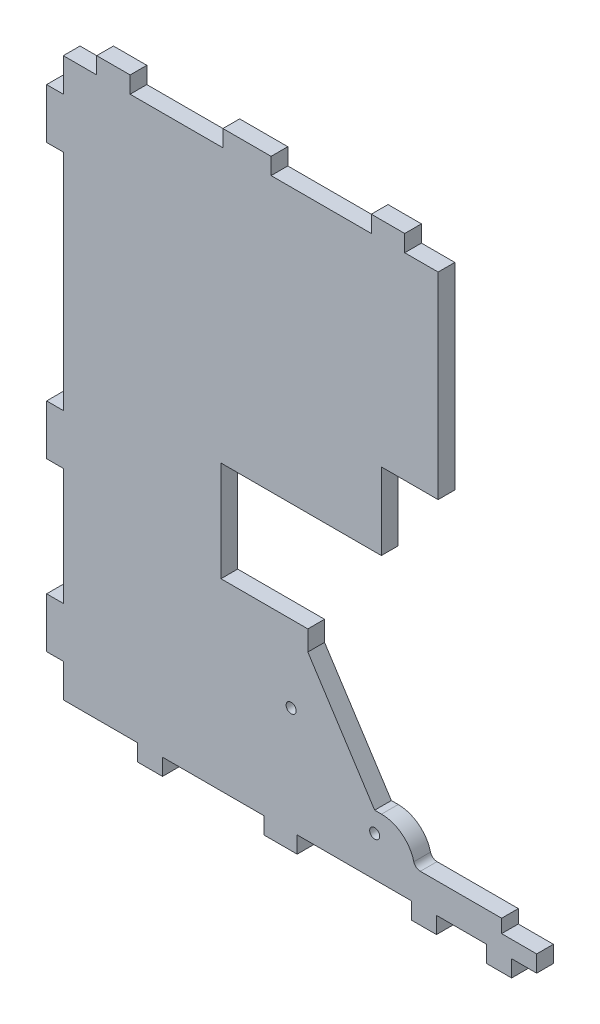
SolidWorks part; units mm, degrees
ref_plane "Plan de face" through (0, 0, 0) normal (0, 0, 1) x (1, 0, 0)
ref_plane "Plan de dessus" through (0, 0, 0) normal (0, 1, 0) x (1, 0, 0)
ref_plane "Plan de droite" through (0, 0, 0) normal (1, 0, 0) x (0, 0, -1)
sketch "Esquisse1" plane through (0, 0, 0) normal (0, 0, 1) x (1, 0, 0)
  line L0 (11, 49) -> (31, 18)
  line L1 (0, 0) -> (37, 0)
  line L2 (0, 0) -> (0, 55)
  line L3 (0, 55) -> (11, 55)
  line L4 (37, 0) -> (37, 18)
  line L6 (11, 55) -> (11, 49)
  line L7 (31, 18) -> (37, 18)
  circle A0 centre (6, 32) radius 1.5
  circle A1 centre (31, 12) radius 1.5
  dimension "D3" = 20
  dimension "D4" = 3
  dimension "D1" = 6
  dimension "D2" = 55
  dimension "D5" = 12
  dimension "D6" = 6
  dimension "D7" = 25
  dimension "D8" = 11
  dimension "D9" = 6
  dimension "D10" = 6
  dimension "D11" = 6
extrude "Boss.-Extru.1" add sketch "Esquisse1" along normal blind 5
sketch "Esquisse2" plane through (0, 0, 5) normal (0, 0, 1) x (1, 0, 0)
  line L0 (37, 18) -> (31, 18) construction
  line L1 (37, 0) -> (42, 0)
  line L2 (37, 0) -> (37, 18)
  line L3 (49.5, 0) -> (64.5, 0)
  line L4 (11, 55) -> (0, 55) construction
  line L5 (72, 0) -> (72, -5)
  line L6 (72, -5) -> (64.5, -5)
  line L7 (64.5, 0) -> (64.5, -5)
  line L8 (72, 0) -> (79.5, 0)
  line L9 (49.5, 0) -> (49.5, -5)
  line L10 (49.5, -5) -> (42, -5)
  line L11 (42, 0) -> (42, -5)
  line L13 (0, 0) -> (0, 55)
  line L14 (0, 55) -> (-15, 55)
  line L15 (40, 167) -> (50, 167)
  line L16 (0, 0) -> (-32.5, 0)
  line L17 (-40, 0) -> (-40, -5)
  line L18 (-15, 55) -> (-15, 85)
  line L19 (-40, -5) -> (-32.5, -5)
  line L20 (-62.19, 0) -> (-62.19, 10)
  line L21 (-62.19, 167) -> (-52.19, 167)
  line L22 (-32.5, 0) -> (-32.5, -5)
  line L23 (33, 85) -> (-15, 85)
  line L24 (50, 167) -> (50, 108)
  line L28 (-40, 0) -> (-62.19, 0)
  line L29 (-52.19, 167) -> (-52.19, 172)
  line L30 (-52.19, 172) -> (-42.19, 172)
  line L31 (-42.19, 167) -> (-42.19, 172)
  line L32 (-42.19, 167) -> (30, 167)
  line L33 (40, 167) -> (40, 172)
  line L34 (40, 172) -> (30, 172)
  line L35 (30, 167) -> (30, 172)
  line L36 (-62.19, 157) -> (-62.19, 167)
  line L37 (-62.19, 10) -> (-67.19, 10)
  line L38 (33, 85) -> (33, 108)
  line L39 (33, 108) -> (50, 108)
  line L40 (37, 18) -> (43, 18)
  line L41 (-62.19, 25) -> (-67.19, 25)
  line L42 (-67.19, 10) -> (-67.19, 25)
  line L43 (-62.19, 60) -> (-67.19, 60)
  line L44 (-62.19, 25) -> (-62.19, 60)
  line L45 (-62.19, 75) -> (-67.19, 75)
  line L46 (-67.19, 60) -> (-67.19, 75)
  line L47 (-62.19, 157) -> (-67.19, 157)
  line L48 (-62.19, 75) -> (-62.19, 142)
  line L49 (-62.19, 142) -> (-67.19, 142)
  line L50 (-67.19, 157) -> (-67.19, 142)
  line L51 (79.5, 0) -> (79.5, 5)
  line L52 (43, 18) -> (43, 9)
  line L53 (43, 9) -> (69, 9)
  line L56 (69, 9) -> (69, 5)
  line L57 (69, 5) -> (79.5, 5)
  circle A0 centre (31, 12) radius 1.5 construction
  dimension "D24" = 3
  dimension "D25" = 12
  dimension "D1" = 42.5
  dimension "D2" = 7.5
  dimension "D3" = 5
  dimension "D4" = 5
  dimension "D5" = 15
  dimension "D6" = 15
  dimension "D7" = 30
  dimension "D8" = 167
  dimension "D9" = 23
  dimension "D10" = 22.19
  dimension "D11" = 32.5
  dimension "D12" = 62.19
  dimension "D13" = 50
  dimension "D14" = 5
  dimension "D15" = 10
  dimension "D16" = 10
  dimension "D17" = 10
  dimension "D18" = 17
  dimension "D19" = 10
  dimension "D20" = 10
  dimension "D21" = 35
  dimension "D22" = 15
  dimension "D23" = 5
  dimension "D26" = 5
  dimension "D27" = 26
  dimension "D28" = 5
extrude "Boss.-Extru.2" add sketch "Esquisse2" against normal blind 5
fillet "Congé1" radius 10 1 edges at (43, 18, 2.5)
fillet "Congé2" radius 2 1 edges at (43, 9, 2.5)
sketch "Esquisse4" plane through (0, 0, 5) normal (0, 0, 1) x (1, 0, 0)
  line L0 (-32.5, 0) -> (42, 0) construction
  line L1 (-2.19, 0) -> (7.81, 0)
  line L2 (-2.19, 0) -> (-2.19, -5)
  line L3 (-2.19, -5) -> (7.81, -5)
  line L4 (7.81, 0) -> (7.81, -5)
  line L5 (-62.19, 10) -> (-62.19, 0) construction
  dimension "D1" = 10
  dimension "D2" = 5
  dimension "D3" = 60
extrude "Boss.-Extru.3" add sketch "Esquisse4" against normal blind 5
sketch "Esquisse5" plane through (0, 0, 5) normal (0, 0, 1) x (1, 0, 0)
  line L0 (30, 167) -> (-42.19, 167) construction
  line L1 (-14.4156, 172) -> (0, 172)
  line L2 (-14.4156, 172) -> (-14.4156, 167)
  line L3 (-14.4156, 167) -> (0, 167)
  line L4 (0, 172) -> (0, 167)
extrude "Boss.-Extru.4" add sketch "Esquisse5" against normal blind 5
